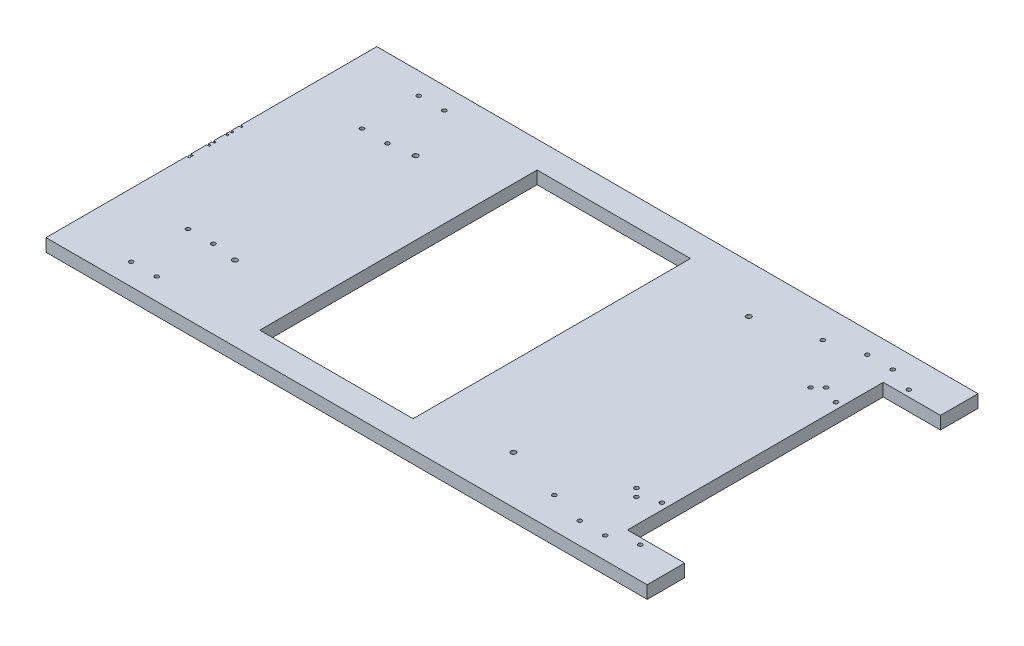
SolidWorks part; units mm, degrees
material "Magnesium Alloy"
ref_plane "Front Plane" through (0, 0, 0) normal (0, 0, 1) x (1, 0, 0)
ref_plane "Top Plane" through (0, 0, 0) normal (0, 1, 0) x (1, 0, 0)
ref_plane "Right Plane" through (0, 0, 0) normal (1, 0, 0) x (0, 0, -1)
sketch "Sketch1" plane through (0, 0, 0) normal (0, 1, 0) x (1, 0, 0)
  line L0 (0, 471.9498) -> (0, -504.9384) construction
  line L1 (-300.0375, 165.1) -> (300.0375, 165.1)
  line L2 (-300.0375, 165.1) -> (-300.0375, -165.1)
  line L3 (-300.0375, -165.1) -> (300.0375, -165.1)
  line L4 (300.0375, 165.1) -> (300.0375, -165.1)
  line L5 (-636.3607, 0) -> (748.0963, 0) construction
  dimension "D1" = 600.075
  dimension "D2" = 330.2
extrude "Boss-Extrude1" add sketch "Sketch1" along normal blind 12.7
sketch "Sketch2" plane through (-300.0375, 0, 0) normal (-1, 0, 0) x (0, 0, 1)
  line L0 (-165.1, 6.35) -> (165.1, 6.35) construction
  line L1 (-165.1, 12.7) -> (-165.1, 0) construction
  line L2 (165.1, 12.7) -> (165.1, 0) construction
  text T0 "Back" font "Century Gothic" height 19.05
extrude "Cut-Extrude1" cut sketch "Sketch2" against normal blind 2.54
sketch "Sketch3" plane through (300.0375, 0, 0) normal (1, 0, 0) x (0, 0, -1)
  line L0 (-165.1, 6.35) -> (165.1, 6.35) construction
  line L1 (-165.1, 12.7) -> (-165.1, 0) construction
  line L2 (165.1, 12.7) -> (165.1, 0) construction
  text T0 "Front" font "Century Gothic" height 19.05
extrude "Cut-Extrude2" cut sketch "Sketch3" against normal blind 2.54
sketch "Sketch4" plane through (0, 0, 0) normal (0, -1, 0) x (1, 0, 0)
  line L0 (407.1831, 0) -> (-551.8052, 0) construction
  line L1 (-113.3475, 138.43) -> (39.6875, 138.43)
  line L2 (-113.3475, 138.43) -> (-113.3475, -138.43)
  line L3 (-113.3475, -138.43) -> (39.6875, -138.43)
  line L4 (39.6875, 138.43) -> (39.6875, -138.43)
  line L5 (55, 0) -> (-55, 0) construction
  line L6 (-300.0375, -165.1) -> (-300.0375, 165.1) construction
  line L7 (300.0375, 165.1) -> (300.0375, -165.1) construction
  line L10 (-300.0375, 165.1) -> (300.0375, 165.1) construction
  dimension "D1" = 186.69
  dimension "D2" = 260.35
  dimension "D3" = 26.67
extrude "Cut-Extrude3" cut sketch "Sketch4" against normal up to next
ref_plane "Plane1" through (223.8375, 0, 0) normal (1, 0, 0) x (0, 0, -1)
ref_plane "Plane2" through (-223.8375, 0, 0) normal (-1, 0, 0) x (0, 0, 1)
sketch "Sketch7" plane through (0, 12.7, 0) normal (0, 1, 0) x (1, 0, 0)
  line L0 (-300.0375, -24.7452) -> (-300.0375, -165.1) construction
  line L1 (-300.0375, -165.1) -> (300.0375, -165.1) construction
  point P0 (-236.5375, -91.2978)
  point P1 (-236.5375, -135.2474)
  point P2 (-211.1375, -135.2474)
  point P3 (-211.1375, -91.2978)
  dimension "D1" = 63.5
  dimension "D2" = 63.5
  dimension "D3" = 88.9
  dimension "D4" = 88.9
  dimension "D5" = 29.8526
  dimension "D6" = 29.8526
  dimension "D7" = 43.9496
  dimension "D8" = 43.9496
sketch "Sketch12" plane through (0, 12.7, 0) normal (0, 1, 0) x (1, 0, 0)
  point P0 (78.8458, -130.175)
ref_plane "Plane3" through (0, 0, 130.175) normal (0, 0, 1) x (1, 0, 0)
sketch "Sketch13" plane through (0, 0, 130.175) normal (0, 0, 1) x (1, 0, 0)
  line L0 (78.8458, 65.775) -> (78.8458, -43.461) construction
hole_wizard "Ø5.0mm Dowel Hole2" positions "Sketch16" profile "Sketch17" hole size "Ø5.0" standard "ANSI Metric" end condition through all
sketch "Sketch16" plane through (0, 12.7, 0) normal (0, 1, 0) x (1, 0, 0)
  line L0 (300.0375, 165.1) -> (-300.0375, 165.1) construction
  line L1 (-300.0375, -165.1) -> (300.0375, -165.1) construction
  line L2 (300.0375, 27.9644) -> (300.0375, 165.1) construction
  line L3 (300.0375, -165.1) -> (300.0375, -28.9413) construction
  circle A1 centre (118.8508, 117.475) radius 2.54
  circle A2 centre (-186.3725, 90.17) radius 2.54
  circle A3 centre (-186.3725, -90.17) radius 2.54
  point P9 (118.8508, 117.475)
  point P12 (-186.3725, 90.17)
  point P21 (-186.3725, -90.17)
  point P51 (118.8508, -117.475)
  dimension "D1" = 47.625
  dimension "D2" = 47.625
  dimension "D3" = 181.1867
  dimension "D4" = 5.08
  dimension "D5" = 181.1867
sketch "Sketch17" plane through (118.8508, 12.7, -117.475) normal (1, 0, 0) x (0, 0, 1)
  line L0 (0, 0) -> (0, 12.7)
  line L1 (0, 12.7) -> (2.5, 12.7)
  line L2 (2.5, 12.7) -> (2.5, 0)
  line L5 (2.5, 0) -> (0, 0)
  line L11 (0, -6.35) -> (0, 107.95) construction
  dimension "Thru Hole Dia." = 5
  dimension "Thru Hole Depth" = 12.7
sketch "Sketch18" plane through (0, 12.7, 0) normal (0, 1, 0) x (1, 0, 0)
  line L0 (300.0375, 27.9644) -> (300.0375, 165.1) construction
  line L1 (300.0375, 127.635) -> (242.8875, 127.635)
  line L2 (300.0375, 127.635) -> (300.0375, -127.635)
  line L3 (300.0375, -127.635) -> (242.8875, -127.635)
  line L4 (242.8875, 127.635) -> (242.8875, -127.635)
  line L5 (300.0375, 165.1) -> (-300.0375, 165.1) construction
  line L6 (-300.0375, -165.1) -> (300.0375, -165.1) construction
  dimension "D1" = 37.465
  dimension "D2" = 37.465
  dimension "D3" = 57.15
extrude "Cut-Extrude4" cut sketch "Sketch18" against normal up to next
sketch "Sketch19" plane through (0, 12.7, 0) normal (0, -1, 0) x (-1, 0, 0)
  circle A0 centre (-218.7586, 94.615) radius 2.032
  circle A1 centre (-218.7586, 94.615) radius 2.032 construction
  circle A2 centre (-218.7586, -94.615) radius 2.032
  circle A3 centre (-218.7586, -94.615) radius 2.032 construction
  circle A4 centre (-176.2125, 133.985) radius 2.032
  circle A5 centre (-176.2125, 133.985) radius 2.032 construction
  circle A6 centre (-176.2125, -133.985) radius 2.032
  circle A7 centre (-176.2125, -133.985) radius 2.032 construction
extrude "Cut-Extrude5" cut sketch "Sketch19" along normal blind 12.7
ref_axis "Axis5" through (176.2125, 0, -133.985) along (0, 1, 0)
ref_axis "Axis6" through (176.2125, 0, 133.985) along (0, 1, 0)
ref_axis "Axis7" through (218.7586, 0, -94.615) along (0, 1, 0)
ref_axis "Axis8" through (218.7586, 0, 94.615) along (0, 1, 0)
sketch "Sketch20" plane through (0, 12.7, 0) normal (0, 1, 0) x (1, 0, 0)
  line L0 (300.0375, 165.1) -> (-300.0375, 165.1) construction
  line L1 (300.0375, 127.635) -> (300.0375, 165.1) construction
  circle A0 centre (236.5375, 143.51) radius 2.0193
  dimension "D1" = 21.59
  dimension "D2" = 63.5
extrude "Cut-Extrude6" cut sketch "Sketch20" against normal up to next
sketch "Sketch21" plane through (0, 12.7, 0) normal (0, 1, 0) x (1, 0, 0)
  line L0 (300.0375, 165.1) -> (-300.0375, 165.1) construction
  line L1 (300.0375, 127.635) -> (300.0375, 165.1) construction
  circle A0 centre (211.1375, 143.51) radius 2.0193
  circle A1 centre (211.1375, 86.86) radius 2.0193
  circle A2 centre (236.5375, 86.86) radius 2.0193
  circle A3 centre (236.5375, 143.51) radius 2.0193 construction
  dimension "D1" = 21.59
  dimension "D2" = 25.4
  dimension "D3" = 4.0386
  dimension "D4" = 78.24
  dimension "D5" = 78.24
  dimension "D6" = 63.5
  dimension "D7" = 4.0386
  dimension "D8" = 25.4
  dimension "D9" = 4.0386
extrude "Cut-Extrude7" cut sketch "Sketch21" against normal up to next
pattern_linear "LPattern1" count 2 spacing 447.675 along (-1, 0, 0) of "Cut-Extrude7", "Cut-Extrude6"
mirror "Mirror5" about plane through (0, 0, 0) normal (0, 0, 1) of "LPattern1"
sketch "Sketch22" plane through (0, 12.7, 0) normal (0, 1, 0) x (1, 0, 0)
  line L0 (300.0375, -165.1) -> (300.0375, -127.635) construction
  line L1 (160.3375, -127.635) -> (300.0375, -127.635) construction
  circle A0 centre (261.9375, -133.985) radius 2.032
  dimension "D1" = 4.064
  dimension "D2" = 38.1
  dimension "D3" = 6.35
extrude "Cut-Extrude8" cut sketch "Sketch22" against normal up to next
mirror "Mirror6" about plane through (0, 0, 0) normal (0, 0, 1) of "Cut-Extrude8"
sketch "Sketch23" plane through (0, 12.7, 0) normal (0, 1, 0) x (1, 0, 0)
  circle A0 centre (-236.5375, 143.51) radius 2.0193
  circle A1 centre (-236.5375, 143.51) radius 3.6068
  circle A2 centre (-211.1375, 143.51) radius 2.0193
  circle A3 centre (-211.1375, 143.51) radius 3.6068
  circle A8 centre (-236.5375, 86.86) radius 2.0193
  circle A9 centre (-236.5375, 86.86) radius 3.6068
  circle A12 centre (-211.1375, 86.86) radius 2.0193
  circle A13 centre (-211.1375, 86.86) radius 3.6068
  circle A16 centre (-186.3725, 90.17) radius 2.5006
  circle A17 centre (-186.3725, 90.17) radius 4.0881
  circle A18 centre (118.8508, 117.475) radius 2.5006
  circle A19 centre (118.8508, 117.475) radius 4.0881
  circle A20 centre (176.2125, 133.985) radius 2.032
  circle A21 centre (211.1375, 86.86) radius 2.0193
  circle A23 centre (218.7586, 94.615) radius 2.032
  circle A25 centre (211.1375, 143.51) radius 2.0193
  circle A26 centre (236.5375, 143.51) radius 2.0193
  circle A28 centre (236.5375, 86.86) radius 2.0193
  circle A30 centre (261.9375, 133.985) radius 2.032
  circle A31 centre (176.2125, 133.985) radius 3.6195
  circle A32 centre (211.1375, 143.51) radius 3.6068
  circle A34 centre (211.1375, 86.86) radius 3.6068
  circle A36 centre (218.7586, 94.615) radius 3.6195
  circle A38 centre (236.5375, 86.86) radius 3.6068
  circle A40 centre (236.5375, 143.51) radius 3.6068
  circle A41 centre (261.9375, 133.985) radius 3.6195
  dimension "D1" = 1.5875
  dimension "D3" = 1.5875
  dimension "D9" = 1.5875
  dimension "D10" = 4.0386
  dimension "D11" = 4.0386
  dimension "D14" = 5.0013
  dimension "D15" = 4.0386
  dimension "D17" = 4.0386
  dimension "D19" = 1.5875
  dimension "D20" = 4.064
  dimension "D21" = 1.5875
  dimension "D22" = 1.5875
  dimension "D24" = 1.5875
  dimension "D26" = 1.5875
  dimension "D28" = 1.5875
  dimension "D31" = 1.5875
  dimension "D32" = 5.0013
  dimension "D34" = 4.0386
  dimension "D35" = 4.064
  dimension "D39" = 4.0386
  dimension "D40" = 4.0386
  dimension "D42" = 4.064
extrude "Boss-Extrude2" add sketch "Sketch23" against normal up to surface (12.7 mm away) up to face at (261.9375, 0, -131.953)
mirror "Mirror10" about plane through (0, 0, 0) normal (0, 0, 1) of "Boss-Extrude2"
sketch "Sketch26" plane through (0, 12.7, 0) normal (0, 1, 0) x (1, 0, 0)
  line L0 (-256.8575, 165.1) -> (-256.8575, 66.04)
  line L2 (-167.9575, 66.04) -> (-167.9575, 104.14)
  line L4 (-99.0313, 148.5171) -> (-73.6313, 148.5171)
  line L10 (177.4799, 0) -> (-282.3425, 0) construction
  line L16 (-99.0313, -148.5171) -> (-73.6313, -148.5171)
  line L18 (-167.9575, -66.04) -> (-167.9575, -104.14)
  line L20 (-256.8575, -165.1) -> (-256.8575, -66.04)
  line L21 (-256.8575, 165.1) -> (-300.0375, 165.1)
  line L22 (-300.0375, 165.1) -> (-300.0375, -165.1)
  line L23 (-300.0375, -165.1) -> (-256.8575, -165.1)
  line L26 (242.8875, 46.4819) -> (242.8875, -46.4819)
  line L29 (-300.0375, 165.1) -> (-300.0375, 29.3077) construction
  line L30 (-300.0375, -165.1) -> (300.0375, -165.1) construction
  line L31 (300.0375, 165.1) -> (-300.0375, 165.1) construction
  line L32 (-167.9575, 66.04) -> (-167.9575, -66.04)
  line L33 (-256.8575, 66.04) -> (-256.8575, -66.04)
  line L34 (242.8875, 127.635) -> (242.8875, -127.635) construction
  line L35 (40.5224, 104.0777) -> (132.8834, 104.0777)
  line L36 (132.8834, 104.0777) -> (132.8834, -104.0777)
  line L37 (132.8834, -104.0777) -> (40.5224, -104.0777)
  line L38 (-73.6313, -148.5171) -> (40.5224, -148.5171)
  line L39 (40.5224, -148.5171) -> (40.5224, -104.0777)
  line L40 (-99.0313, -148.5171) -> (-167.9575, -148.5171)
  line L41 (-167.9575, -148.5171) -> (-167.9575, -104.14)
  line L42 (-73.6313, 148.5171) -> (40.5224, 148.5171)
  line L43 (40.5224, 148.5171) -> (40.5224, 104.0777)
  line L44 (-99.0313, 148.5171) -> (-167.9575, 148.5171)
  line L45 (-167.9575, 148.5171) -> (-167.9575, 104.14)
  line L46 (242.8875, 46.4819) -> (197.2404, 46.4819)
  line L47 (197.2404, 46.4819) -> (197.2404, -46.4819)
  line L48 (197.2404, -46.4819) -> (242.8875, -46.4819)
  dimension "D1" = 88.9
  dimension "D2" = 99.06
  dimension "D3" = 38.1
  dimension "D4" = 25.4
  dimension "D5" = 43.18
sketch "Sketch27" plane through (0, 12.7, 0) normal (0, 1, 0) x (1, 0, 0)
  line L0 (-60.0798, 0) -> (60.0798, 0) construction
  circle A0 centre (-236.5375, 143.51) radius 2.0193
  circle A1 centre (-236.5375, 143.51) radius 3.175
  circle A2 centre (-211.1375, 143.51) radius 2.0193
  circle A3 centre (-211.1375, 143.51) radius 3.175
  circle A4 centre (-236.5375, 86.86) radius 2.0193
  circle A5 centre (-236.5375, 86.86) radius 3.175
  circle A6 centre (-211.1375, 86.86) radius 2.0193
  circle A7 centre (-211.1375, 86.86) radius 3.175
  circle A8 centre (236.5375, 86.86) radius 2.0193
  circle A9 centre (236.5375, 86.86) radius 3.175
  circle A10 centre (211.1375, 86.86) radius 2.0193
  circle A11 centre (211.1375, 86.86) radius 3.175
  circle A12 centre (211.1375, 143.51) radius 2.0193
  circle A13 centre (211.1375, 143.51) radius 3.175
  circle A14 centre (236.5375, 143.51) radius 2.0193
  circle A15 centre (236.5375, 143.51) radius 3.175
  circle A16 centre (236.5375, -143.51) radius 3.175
  circle A17 centre (236.5375, -143.51) radius 2.0193
  circle A18 centre (211.1375, -143.51) radius 3.175
  circle A19 centre (211.1375, -143.51) radius 2.0193
  circle A20 centre (211.1375, -86.86) radius 3.175
  circle A21 centre (211.1375, -86.86) radius 2.0193
  circle A22 centre (236.5375, -86.86) radius 3.175
  circle A23 centre (236.5375, -86.86) radius 2.0193
  circle A24 centre (-211.1375, -86.86) radius 3.175
  circle A25 centre (-211.1375, -86.86) radius 2.0193
  circle A26 centre (-236.5375, -86.86) radius 3.175
  circle A27 centre (-236.5375, -86.86) radius 2.0193
  circle A28 centre (-211.1375, -143.51) radius 3.175
  circle A29 centre (-211.1375, -143.51) radius 2.0193
  circle A30 centre (-236.5375, -143.51) radius 3.175
  circle A31 centre (-236.5375, -143.51) radius 2.0193
  dimension "D1" = 6.35
sketch "Sketch28" plane through (0, 12.7, 0) normal (0, 1, 0) x (1, 0, 0)
  line L0 (-60.0798, 0) -> (60.0798, 0) construction
  circle A0 centre (-186.3725, 90.17) radius 2.5
  circle A1 centre (-186.3725, 90.17) radius 3.175
  circle A2 centre (118.8508, 117.475) radius 2.5
  circle A3 centre (118.8508, 117.475) radius 3.175
  circle A4 centre (176.2125, 133.985) radius 2.032
  circle A5 centre (176.2125, 133.985) radius 3.175
  circle A6 centre (218.7586, 94.615) radius 2.032
  circle A7 centre (218.7586, 94.615) radius 3.175
  circle A8 centre (218.7586, -94.615) radius 3.175
  circle A9 centre (218.7586, -94.615) radius 2.032
  circle A10 centre (176.2125, -133.985) radius 3.175
  circle A11 centre (176.2125, -133.985) radius 2.032
  circle A12 centre (118.8508, -117.475) radius 3.175
  circle A13 centre (118.8508, -117.475) radius 2.5
  circle A14 centre (-186.3725, -90.17) radius 3.175
  circle A15 centre (-186.3725, -90.17) radius 2.5
  circle A16 centre (261.9375, 133.985) radius 2.032
  circle A17 centre (261.9375, 133.985) radius 3.175
  circle A18 centre (261.9375, -133.985) radius 2.032
  circle A19 centre (261.9375, -133.985) radius 3.175
  dimension "D1" = 6.35
  dimension "D2" = 6.35
  dimension "D3" = 6.35
